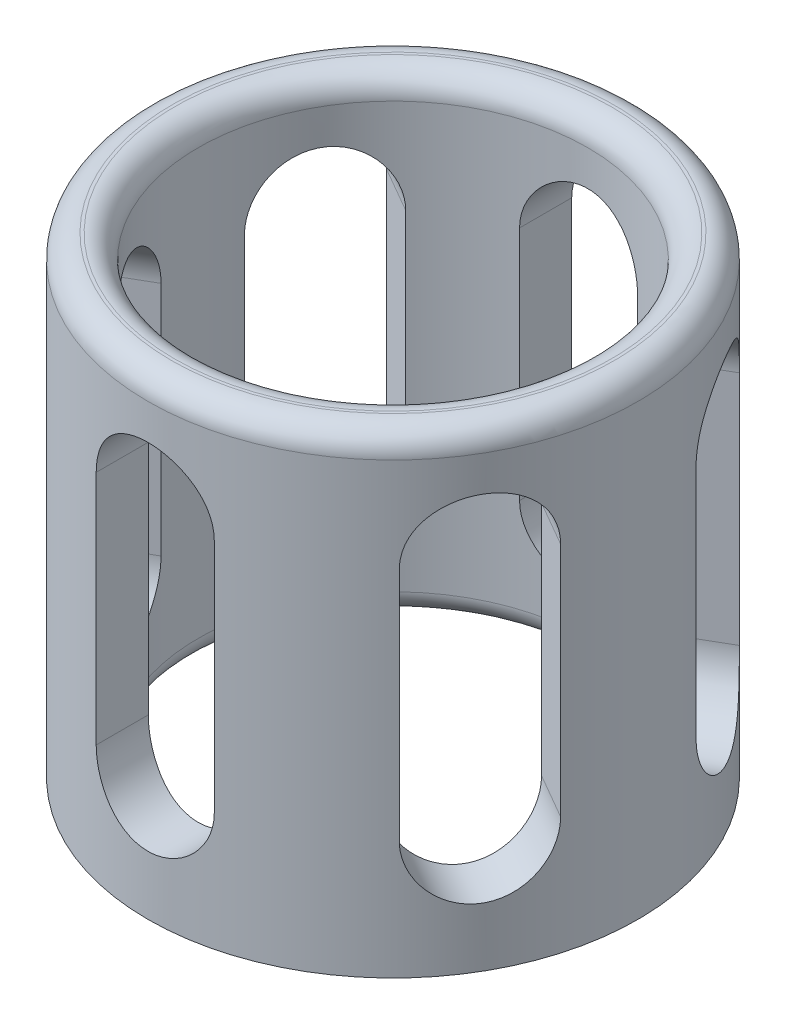
SolidWorks part; units mm, degrees
ref_plane "Front" through (0, 0, 0) normal (0, 0, 1) x (1, 0, 0)
ref_plane "Top" through (0, 0, 0) normal (0, 1, 0) x (1, 0, 0)
ref_plane "Right" through (0, 0, 0) normal (1, 0, 0) x (0, 0, -1)
sketch "Sketch1" plane through (0, 0, 0) normal (0, 1, 0) x (1, 0, 0)
  circle A0 centre (0, 0) radius 20.75
  circle A1 centre (0, 0) radius 16.5
  dimension "D1" = 41.5
  dimension "D2" = 33
extrude "Boss-Extrude1" add sketch "Sketch1" along normal blind 40
ref_plane "Plane1" through (0, 0, 20.75) normal (0, 0, 1) x (1, 0, 0)
sketch "Sketch2" plane through (0, 0, 20.75) normal (0, 0, 1) x (1, 0, 0)
  line L0 (0, 40) -> (0, 0) construction
  line L1 (20.75, 40) -> (-20.75, 40) construction
  line L2 (-20.75, 0) -> (20.75, 0) construction
  line L3 (-5, 20) -> (5, 20) construction
  line L4 (-5, 30) -> (5, 30)
  line L5 (-5, 30) -> (-5, 10)
  line L6 (-5, 10) -> (5, 10)
  line L7 (5, 30) -> (5, 10)
  line L8 (-5, 30) -> (5, 10) construction
  line L9 (-5, 10) -> (5, 30) construction
  arc A0 (-5, 30) -> (5, 30) centre (0, 30) cw
  arc A1 (-5, 10) -> (5, 10) centre (0, 10) ccw
  point P6 (0, 20)
  dimension "D1" = 10
  dimension "D2" = 20
extrude "Cut-Extrude1" cut sketch "Sketch2" against normal blind 20 contours L6 A1 | L7 L4 L5 L6 | A0 L4 region at (0, 32.1221, 20.75) region at (0, 20, 20.75) region at (0, 7.8779, 20.75)
pattern_circular "CirPattern1" count 6 over 360 about axis through (0, 40, 0) along (0, -1, 0) of "Cut-Extrude1"
fillet "Fillet1" radius 2 3 edges at (0, 40, 20.75) (0, 0, 16.5) (0, 40, 16.5)
